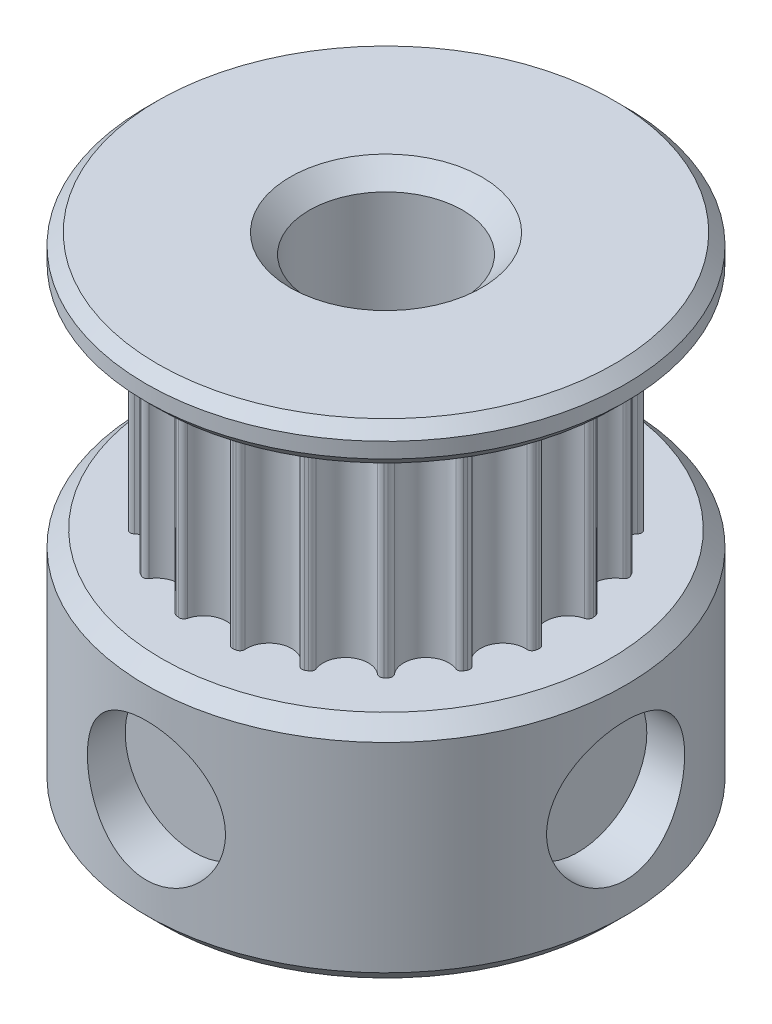
SolidWorks part; units mm, degrees
ref_plane "Front Plane" through (0, 0, 0) normal (0, 0, 1) x (1, 0, 0)
ref_plane "Top Plane" through (0, 0, 0) normal (0, 1, 0) x (1, 0, 0)
ref_plane "Right Plane" through (0, 0, 0) normal (1, 0, 0) x (0, 0, -1)
ref_plane "Plane1" through (0, 0, 0) normal (0, 0, -1) x (-1, 0, 0)
sketch "Sketch1" plane through (0, 0, 0) normal (0, 0, -1) x (-1, 0, 0)
  line L0 (-7.5565, 14.859) -> (0, 14.859)
  line L1 (0, 14.859) -> (0, 16.129)
  line L2 (0, 16.129) -> (-7.5565, 16.129)
  line L3 (-7.5565, 16.129) -> (-7.9375, 15.748)
  line L4 (-7.9375, 15.748) -> (-7.9375, 15.24)
  line L5 (-7.9375, 15.24) -> (-7.5565, 14.859)
  line L6 (0, 14.859) -> (0, 16.129) construction
revolve "Revolve1" add sketch "Sketch1" angle 360 about L6 reverse direction yes
sketch "Sketch2" plane through (0, 14.859, 0) normal (0, -1, 0) x (1, 0, 0)
  arc A0 (4.3011, 4.2298) -> (4.4027, 4.124) centre (0, 0) cw
  arc A1 (4.4027, 4.124) -> (5.2827, 2.9128) centre (4.8804, 3.5458) ccw
  arc A2 (5.2827, 2.9128) -> (5.3519, 2.7835) centre (0, 0) cw
  arc A3 (5.3977, 2.6937) -> (5.4616, 2.5617) centre (0, 0) cw
  arc A4 (5.4616, 2.5617) -> (5.9242, 1.1378) centre (5.7372, 1.8641) ccw
  arc A5 (5.9242, 1.1378) -> (5.9501, 0.9934) centre (0, 0) cw
  arc A6 (5.9659, 0.8939) -> (5.9859, 0.7485) centre (0, 0) cw
  arc A7 (5.9859, 0.7485) -> (5.9859, -0.7485) centre (6.0325, 0) ccw
  arc A8 (5.9859, -0.7485) -> (5.9659, -0.8939) centre (0, 0) cw
  arc A9 (5.9501, -0.9934) -> (5.9242, -1.1378) centre (0, 0) cw
  arc A10 (5.9242, -1.1378) -> (5.4616, -2.5617) centre (5.7372, -1.8641) ccw
  arc A11 (5.4616, -2.5617) -> (5.3977, -2.6937) centre (0, 0) cw
  arc A12 (5.3519, -2.7835) -> (5.2827, -2.9128) centre (0, 0) cw
  arc A13 (5.2827, -2.9128) -> (4.4027, -4.124) centre (4.8804, -3.5458) ccw
  arc A14 (4.4027, -4.124) -> (4.3011, -4.2298) centre (0, 0) cw
  arc A15 (4.2298, -4.3011) -> (4.124, -4.4027) centre (0, 0) cw
  arc A16 (4.124, -4.4027) -> (2.9128, -5.2827) centre (3.5458, -4.8804) ccw
  arc A17 (2.9128, -5.2827) -> (2.7835, -5.3519) centre (0, 0) cw
  arc A18 (2.6937, -5.3977) -> (2.5617, -5.4616) centre (0, 0) cw
  arc A19 (2.5617, -5.4616) -> (1.1378, -5.9242) centre (1.8641, -5.7372) ccw
  arc A20 (1.1378, -5.9242) -> (0.9934, -5.9501) centre (0, 0) cw
  arc A21 (0.8939, -5.9659) -> (0.7485, -5.9859) centre (0, 0) cw
  arc A22 (0.7485, -5.9859) -> (-0.7485, -5.9859) centre (0, -6.0325) ccw
  arc A23 (-0.7485, -5.9859) -> (-0.8939, -5.9659) centre (0, 0) cw
  arc A24 (-0.9934, -5.9501) -> (-1.1378, -5.9242) centre (0, 0) cw
  arc A25 (-1.1378, -5.9242) -> (-2.5617, -5.4616) centre (-1.8641, -5.7372) ccw
  arc A26 (-2.5617, -5.4616) -> (-2.6937, -5.3977) centre (0, 0) cw
  arc A27 (-2.7835, -5.3519) -> (-2.9128, -5.2827) centre (0, 0) cw
  arc A28 (-2.9128, -5.2827) -> (-4.124, -4.4027) centre (-3.5458, -4.8804) ccw
  arc A29 (-4.124, -4.4027) -> (-4.2298, -4.3011) centre (0, 0) cw
  arc A30 (-4.3011, -4.2298) -> (-4.4027, -4.124) centre (0, 0) cw
  arc A31 (-4.4027, -4.124) -> (-5.2827, -2.9128) centre (-4.8804, -3.5458) ccw
  arc A32 (-5.2827, -2.9128) -> (-5.3519, -2.7835) centre (0, 0) cw
  arc A33 (-5.3977, -2.6937) -> (-5.4616, -2.5617) centre (0, 0) cw
  arc A34 (-5.4616, -2.5617) -> (-5.9242, -1.1378) centre (-5.7372, -1.8641) ccw
  arc A35 (-5.9242, -1.1378) -> (-5.9501, -0.9934) centre (0, 0) cw
  arc A36 (-5.9659, -0.8939) -> (-5.9859, -0.7485) centre (0, 0) cw
  arc A37 (-5.9859, -0.7485) -> (-5.9859, 0.7485) centre (-6.0325, 0) ccw
  arc A38 (-5.9859, 0.7485) -> (-5.9659, 0.8939) centre (0, 0) cw
  arc A39 (-5.9501, 0.9934) -> (-5.9242, 1.1378) centre (0, 0) cw
  arc A40 (-5.9242, 1.1378) -> (-5.4616, 2.5617) centre (-5.7372, 1.8641) ccw
  arc A41 (-5.4616, 2.5617) -> (-5.3977, 2.6937) centre (0, 0) cw
  arc A42 (-5.3519, 2.7835) -> (-5.2827, 2.9128) centre (0, 0) cw
  arc A43 (-5.2827, 2.9128) -> (-4.4027, 4.124) centre (-4.8804, 3.5458) ccw
  arc A44 (-4.4027, 4.124) -> (-4.3011, 4.2298) centre (0, 0) cw
  arc A45 (-4.2298, 4.3011) -> (-4.124, 4.4027) centre (0, 0) cw
  arc A46 (-4.124, 4.4027) -> (-2.9128, 5.2827) centre (-3.5458, 4.8804) ccw
  arc A47 (-2.9128, 5.2827) -> (-2.7835, 5.3519) centre (0, 0) cw
  arc A48 (-2.6937, 5.3977) -> (-2.5617, 5.4616) centre (0, 0) cw
  arc A49 (-2.5617, 5.4616) -> (-1.1378, 5.9242) centre (-1.8641, 5.7372) ccw
  arc A50 (-1.1378, 5.9242) -> (-0.9934, 5.9501) centre (0, 0) cw
  arc A51 (-0.8939, 5.9659) -> (-0.7485, 5.9859) centre (0, 0) cw
  arc A52 (-0.7485, 5.9859) -> (0.7485, 5.9859) centre (0, 6.0325) ccw
  arc A53 (0.7485, 5.9859) -> (0.8939, 5.9659) centre (0, 0) cw
  arc A54 (0.9934, 5.9501) -> (1.1378, 5.9242) centre (0, 0) cw
  arc A55 (1.1378, 5.9242) -> (2.5617, 5.4616) centre (1.8641, 5.7372) ccw
  arc A56 (2.5617, 5.4616) -> (2.6937, 5.3977) centre (0, 0) cw
  arc A57 (2.7835, 5.3519) -> (2.9128, 5.2827) centre (0, 0) cw
  arc A58 (2.9128, 5.2827) -> (4.124, 4.4027) centre (3.5458, 4.8804) ccw
  arc A59 (4.124, 4.4027) -> (4.2298, 4.3011) centre (0, 0) cw
  spline S0 degree 3 poles (5.3977, 2.6937) (5.3827, 2.7238) (5.3674, 2.7537) (5.3519, 2.7835) knots 0 0 0 0 1 1 1 1
  spline S1 degree 3 poles (5.9659, 0.8939) (5.9609, 0.9271) (5.9557, 0.9603) (5.9501, 0.9934) knots 0 0 0 0 1 1 1 1
  spline S2 degree 3 poles (5.9501, -0.9934) (5.9557, -0.9603) (5.9609, -0.9271) (5.9659, -0.8939) knots 0 0 0 0 1 1 1 1
  spline S3 degree 3 poles (5.3519, -2.7835) (5.3674, -2.7537) (5.3827, -2.7238) (5.3977, -2.6937) knots 0 0 0 0 1 1 1 1
  spline S4 degree 3 poles (4.2298, -4.3011) (4.2538, -4.2775) (4.2775, -4.2538) (4.3011, -4.2298) knots 0 0 0 0 1 1 1 1
  spline S5 degree 3 poles (2.6937, -5.3977) (2.7238, -5.3827) (2.7537, -5.3674) (2.7835, -5.3519) knots 0 0 0 0 1 1 1 1
  spline S6 degree 3 poles (0.8939, -5.9659) (0.9271, -5.9609) (0.9603, -5.9557) (0.9934, -5.9501) knots 0 0 0 0 1 1 1 1
  spline S7 degree 3 poles (-0.9934, -5.9501) (-0.9603, -5.9557) (-0.9271, -5.9609) (-0.8939, -5.9659) knots 0 0 0 0 1 1 1 1
  spline S8 degree 3 poles (-2.7835, -5.3519) (-2.7537, -5.3674) (-2.7238, -5.3827) (-2.6937, -5.3977) knots 0 0 0 0 1 1 1 1
  spline S9 degree 3 poles (-4.3011, -4.2298) (-4.2775, -4.2538) (-4.2538, -4.2775) (-4.2298, -4.3011) knots 0 0 0 0 1 1 1 1
  spline S10 degree 3 poles (-5.3977, -2.6937) (-5.3827, -2.7238) (-5.3674, -2.7537) (-5.3519, -2.7835) knots 0 0 0 0 1 1 1 1
  spline S11 degree 3 poles (-5.9659, -0.8939) (-5.9609, -0.9271) (-5.9557, -0.9603) (-5.9501, -0.9934) knots 0 0 0 0 1 1 1 1
  spline S12 degree 3 poles (-5.9501, 0.9934) (-5.9557, 0.9603) (-5.9609, 0.9271) (-5.9659, 0.8939) knots 0 0 0 0 1 1 1 1
  spline S13 degree 3 poles (-5.3519, 2.7835) (-5.3674, 2.7537) (-5.3827, 2.7238) (-5.3977, 2.6937) knots 0 0 0 0 1 1 1 1
  spline S14 degree 3 poles (-4.2298, 4.3011) (-4.2538, 4.2775) (-4.2775, 4.2538) (-4.3011, 4.2298) knots 0 0 0 0 1 1 1 1
  spline S15 degree 3 poles (-2.6937, 5.3977) (-2.7238, 5.3827) (-2.7537, 5.3674) (-2.7835, 5.3519) knots 0 0 0 0 1 1 1 1
  spline S16 degree 3 poles (-0.8939, 5.9659) (-0.9271, 5.9609) (-0.9603, 5.9557) (-0.9934, 5.9501) knots 0 0 0 0 1 1 1 1
  spline S17 degree 3 poles (0.9934, 5.9501) (0.9603, 5.9557) (0.9271, 5.9609) (0.8939, 5.9659) knots 0 0 0 0 1 1 1 1
  spline S18 degree 3 poles (2.7835, 5.3519) (2.7537, 5.3674) (2.7238, 5.3827) (2.6937, 5.3977) knots 0 0 0 0 1 1 1 1
  spline S19 degree 3 poles (4.3011, 4.2298) (4.2775, 4.2538) (4.2538, 4.2775) (4.2298, 4.3011) knots 0 0 0 0 1 1 1 1
extrude "Boss-Extrude1" add sketch "Sketch2" along normal blind 7.239
ref_plane "Plane2" through (0, 7.62, 0) normal (0, 1, 0) x (1, 0, 0)
sketch "Sketch3" plane through (0, 7.62, 0) normal (0, 1, 0) x (1, 0, 0)
  circle A0 centre (0, 0) radius 7.9375
extrude "Boss-Extrude2" add sketch "Sketch3" against normal blind 7.62
hole_wizard "M4 Clearance Hole1" positions "3DSketch1" profile "Sketch4" hole size "M4" standard "ANSI Metric"
sketch3d "3DSketch1"
  point P0 (7.9375, 3.81, 0)
sketch "Sketch4" plane through (7.9375, 3.81, 0) normal (0, 1, 0) x (0, 0, -1)
  line L0 (0, 0) -> (0, 1.5875)
  line L1 (0, 1.5875) -> (2.286, 1.5875)
  line L2 (2.286, 1.5875) -> (2.286, 0)
  line L5 (2.286, 0) -> (0, 0)
  line L10 (0, 1.5875) -> (-2.286, 1.5875) construction
  line L11 (0, -6.35) -> (0, 107.95) construction
  dimension "Hole Dia." = 4.572
  dimension "Hole Depth" = 1.5875
  dimension "Drill Angle" = 180
hole_wizard "M4 Clearance Hole2" positions "3DSketch2" profile "Sketch5" hole size "M4" standard "ANSI Metric"
sketch3d "3DSketch2"
  point P0 (0, 3.81, 7.9375)
sketch "Sketch5" plane through (0, 3.81, 7.9375) normal (1, 0, 0) x (0, -1, 0)
  line L0 (0, 0) -> (0, 1.5875)
  line L1 (0, 1.5875) -> (2.286, 1.5875)
  line L2 (2.286, 1.5875) -> (2.286, 0)
  line L5 (2.286, 0) -> (0, 0)
  line L10 (0, 1.5875) -> (-2.286, 1.5875) construction
  line L11 (0, -6.35) -> (0, 107.95) construction
  dimension "Hole Dia." = 4.572
  dimension "Hole Depth" = 1.5875
  dimension "Drill Angle" = 180
hole_wizard "Hole1" positions "Sketch7" profile "Sketch6" legacy
sketch "Sketch7" plane through (0, 0, 0) normal (0, -1, 0) x (-1, 0, 0)
  point P0 (0, 0)
sketch "Sketch6" plane through (0, 0, 0) normal (1, 0, 0) x (0, 0, -1)
  line L0 (0, 0) -> (0, 16.129)
  line L1 (0, 16.129) -> (2.54, 16.129)
  line L2 (2.54, 16.129) -> (2.54, 0)
  line L3 (2.54, 0) -> (0, 0)
  line L4 (0, 110) -> (0, -10) construction
  dimension "Diameter" = 5.08
  dimension "Depth" = 16.129
chamfer "Chamfer1" distance 0.635 angle 45 2 edges at (0, 16.129, -2.54) (0, 0, -2.54)
chamfer "Chamfer2" distance 0.508 angle 45 2 edges at (0, 0, -7.9375) (0, 7.62, -7.9375)
fillet "Fillet1" radius 0.152 40 edges at (4.124, 11.2395, -4.4027) (-2.9128, 11.2395, -5.2827) (5.4616, 11.2395, 2.5617) (5.2827, 11.2395, 2.9128) (0.7485, 11.2395, -5.9859) (4.4027, 11.2395, 4.124) (5.9242, 11.2395, -1.1378) (4.124, 11.2395, 4.4027) (-4.4027, 11.2395, -4.124) (2.9128, 11.2395, 5.2827) (-1.1378, 11.2395, -5.9242) (2.5617, 11.2395, 5.4616) (2.5617, 11.2395, -5.4616) (1.1378, 11.2395, 5.9242) (5.2827, 11.2395, -2.9128) (0.7485, 11.2395, 5.9859) (5.9859, 11.2395, 0.7485) (-0.7485, 11.2395, 5.9859) (-5.2827, 11.2395, -2.9128) (-1.1378, 11.2395, 5.9242) (-4.124, 11.2395, -4.4027) (-2.5617, 11.2395, 5.4616) (-2.5617, 11.2395, -5.4616) (-2.9128, 11.2395, 5.2827) (-0.7485, 11.2395, -5.9859) (-4.124, 11.2395, 4.4027) (1.1378, 11.2395, -5.9242) (-4.4027, 11.2395, 4.124) (2.9128, 11.2395, -5.2827) (-5.2827, 11.2395, 2.9128) (4.4027, 11.2395, -4.124) (-5.4616, 11.2395, 2.5617) (5.4616, 11.2395, -2.5617) (-5.9242, 11.2395, 1.1378) (5.9859, 11.2395, -0.7485) (-5.9859, 11.2395, 0.7485) (5.9242, 11.2395, 1.1378) (-5.9242, 11.2395, -1.1378) (-5.4616, 11.2395, -2.5617) (-5.9859, 11.2395, -0.7485) tangent propagation no
